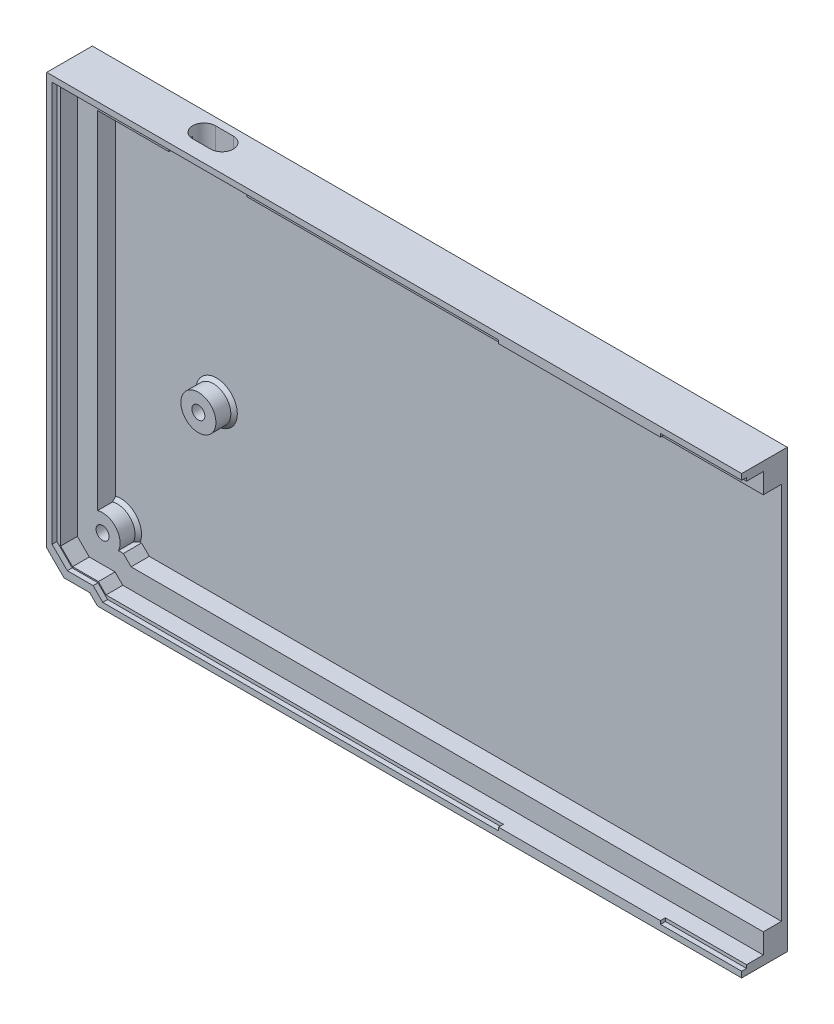
SolidWorks part; units mm, degrees
ref_plane "Přední rovina" through (0, 0, 0) normal (0, 0, 1) x (1, 0, 0)
ref_plane "Horní rovina" through (0, 0, 0) normal (0, 1, 0) x (1, 0, 0)
ref_plane "Pravá rovina" through (0, 0, 0) normal (1, 0, 0) x (0, 0, -1)
sketch "Skica3" plane through (0, 0, 0) normal (0, 0, 1) x (1, 0, 0)
  line L0 (0, 0) -> (415.1053, 0) construction
  line L1 (415.1053, 0) -> (416.6927, -1.5875) construction
  line L2 (416.6927, -1.5875) -> (416.6927, -119.8485) construction
  line L3 (0, 0) -> (-1.5875, -1.5875) construction
  line L4 (-1.5875, -1.5875) -> (-1.5875, -119.8485) construction
  line L5 (-1.5875, -119.8485) -> (0.7934, -122.2292) construction
  line L6 (0.7934, -122.2292) -> (8.7304, -122.2292) construction
  line L7 (8.7304, -122.2292) -> (11.1113, -124.61) construction
  line L8 (11.1113, -124.61) -> (403.9933, -124.61) construction
  line L9 (403.9933, -124.61) -> (406.3744, -122.2294) construction
  line L10 (406.3744, -122.2294) -> (414.3114, -122.2294) construction
  line L11 (416.6927, -119.8485) -> (414.3114, -122.2294) construction
  line L12 (2.4125, -4) -> (412.6927, -4)
  line L13 (412.6927, -4) -> (412.6927, -4)
  line L14 (412.6927, -4) -> (412.6927, -118.1914)
  line L15 (412.6927, -118.1914) -> (412.6547, -118.2294)
  line L16 (404.7177, -118.2294) -> (412.6547, -118.2294)
  line L17 (402.3367, -120.61) -> (404.7177, -118.2294)
  line L18 (12.7681, -120.61) -> (402.3367, -120.61)
  line L19 (10.3872, -118.2292) -> (12.7681, -120.61)
  line L20 (2.4502, -118.2292) -> (10.3872, -118.2292)
  line L21 (2.4125, -118.1915) -> (2.4502, -118.2292)
  line L22 (2.4125, -4) -> (2.4125, -118.1915)
  line L23 (2.4125, -4) -> (2.4125, -4)
  line L24 (-1.5875, -119.8485) -> (415.1053, 0) construction
  line L26 (0, 0) -> (416.6927, -119.8485) construction
  dimension "D1" = 135
  dimension "D2" = 135
  dimension "D3" = 4
  dimension "D4" = 2.245
  dimension "D5" = 2.245
  dimension "D6" = 118.261
  dimension "D7" = 118.261
  dimension "D8" = 3.367
  dimension "D9" = 7.937
  dimension "D10" = 3.367
  dimension "D11" = 392.882
  dimension "D12" = 3.367
  dimension "D13" = 7.937
  dimension "D14" = 3.3674
extrude "Přidat vysunutím1" add sketch "Skica3" along normal blind 5.6
shell "Skořepina1" thickness 1.8 removed face at (207.5525, -95.852, 5.6) outward yes
sketch "Skica7" plane through (0, 0, 5.6) normal (0, 0, 1) x (1, 0, 0)
  line L20 (-6.5875, 5) -> (-6.5875, -121.9196)
  line L21 (-6.5875, -121.9196) -> (-1.2775, -127.2292)
  line L22 (-1.2775, -127.2292) -> (6.6595, -127.2292)
  line L23 (6.6595, -127.2292) -> (9.0403, -129.61)
  line L24 (9.0403, -129.61) -> (406.0641, -129.61)
  line L25 (406.0641, -129.61) -> (408.4452, -127.2294)
  line L26 (408.4452, -127.2294) -> (416.3822, -127.2294)
  line L27 (416.3822, -127.2294) -> (421.6927, -121.9198)
  line L28 (421.6927, -121.9198) -> (421.6927, 5)
  line L29 (421.6927, 5) -> (-6.5875, 5)
  line L30 (-6.5875, 5) -> (-6.5875, -121.9196)
  line L31 (-6.5875, -121.9196) -> (-1.2775, -127.2292)
  line L32 (-1.2775, -127.2292) -> (6.6595, -127.2292)
  line L33 (6.6595, -127.2292) -> (9.0403, -129.61)
  line L34 (9.0403, -129.61) -> (406.0641, -129.61)
  line L35 (406.0641, -129.61) -> (408.4452, -127.2294)
  line L36 (408.4452, -127.2294) -> (416.3822, -127.2294)
  line L37 (416.3822, -127.2294) -> (421.6927, -121.9198)
  line L38 (421.6927, -121.9198) -> (421.6927, 5)
  line L39 (421.6927, 5) -> (-6.5875, 5)
  line L40 (-3.7875, 2.2) -> (-3.7875, -120.7598)
  line L41 (-3.7875, -120.7598) -> (-0.1178, -124.4292)
  line L42 (-0.1178, -124.4292) -> (7.8192, -124.4292)
  line L43 (7.8192, -124.4292) -> (10.2001, -126.81)
  line L44 (10.2001, -126.81) -> (404.9045, -126.81)
  line L45 (404.9045, -126.81) -> (407.2855, -124.4294)
  line L46 (407.2855, -124.4294) -> (415.2225, -124.4294)
  line L47 (415.2225, -124.4294) -> (418.8927, -120.7598)
  line L48 (418.8927, -120.7598) -> (418.8927, 2.2)
  line L49 (418.8927, 2.2) -> (-3.7875, 2.2)
  line L50 (-3.7875, 2.2) -> (-3.7875, -120.7598)
  line L51 (-3.7875, -120.7598) -> (-0.1178, -124.4292)
  line L52 (-0.1178, -124.4292) -> (7.8192, -124.4292)
  line L53 (7.8192, -124.4292) -> (10.2001, -126.81)
  line L54 (10.2001, -126.81) -> (404.9045, -126.81)
  line L55 (404.9045, -126.81) -> (407.2855, -124.4294)
  line L56 (407.2855, -124.4294) -> (415.2225, -124.4294)
  line L57 (415.2225, -124.4294) -> (418.8927, -120.7598)
  line L58 (418.8927, -120.7598) -> (418.8927, 2.2)
  line L59 (418.8927, 2.2) -> (-3.7875, 2.2)
  dimension "D2" = 4.4
  dimension "D1" = 7.2
extrude "Přidat vysunutím3" add sketch "Skica7" along normal blind 5.15 separate body
sketch "Skica8" plane through (0, 0, 5.6) normal (0, 0, -1) x (-1, 0, 0)
  line L0 (-421.6927, 5) -> (6.5875, 5)
  line L1 (6.5875, 5) -> (6.5875, -121.9196)
  line L2 (6.5875, 5) -> (6.5875, -121.9196) construction
  line L3 (6.5875, -121.9196) -> (1.2775, -127.2292)
  line L4 (1.2775, -127.2292) -> (-6.6595, -127.2292)
  line L5 (-6.6595, -127.2292) -> (-9.0403, -129.61)
  line L6 (-9.0403, -129.61) -> (-406.0641, -129.61)
  line L7 (-406.0641, -129.61) -> (-408.4452, -127.2294)
  line L8 (-408.4452, -127.2294) -> (-416.3822, -127.2294)
  line L9 (-416.3822, -127.2294) -> (-421.6927, -121.9198)
  line L10 (-421.6927, -121.9198) -> (-421.6927, 5)
  line L11 (-0.6125, -2.2) -> (-0.6125, -118.9371)
  line L12 (-414.4927, -2.2) -> (-0.6125, -2.2) construction
  line L13 (-0.6125, -2.2) -> (-0.6125, -118.9371) construction
  line L14 (-0.6125, -118.9371) -> (-1.7047, -120.0292)
  line L15 (-1.7047, -120.0292) -> (-9.6417, -120.0292)
  line L16 (-9.6417, -120.0292) -> (-12.0226, -122.41)
  line L17 (-12.0226, -122.41) -> (-403.0822, -122.41)
  line L18 (-403.0822, -122.41) -> (-405.4632, -120.0294)
  line L19 (-405.4632, -120.0294) -> (-413.4002, -120.0294) construction
  line L20 (-405.4632, -120.0294) -> (-413.4002, -120.0294)
  line L21 (-413.4002, -120.0294) -> (-414.4927, -118.9371) construction
  line L22 (-413.4002, -120.0294) -> (-414.4927, -118.9371)
  line L23 (-414.4927, -118.9371) -> (-414.4927, -2.2)
  line L24 (-414.4927, -2.2) -> (-0.6125, -2.2)
extrude "Přidat vysunutím4" add sketch "Skica8" along normal up to surface (7.4 mm away) up to face at (207.5525, -96.7211, -1.8)
sketch "Skica11" plane through (0, 0, 10.75) normal (0, 0, 1) x (1, 0, 0)
  line L0 (207.5526, 3.195) -> (207.5526, 5) construction
  line L1 (421.6927, 5) -> (-6.5875, 5) construction
  line L2 (207.5522, -127.805) -> (207.5522, -129.61) construction
  line L3 (9.0403, -129.61) -> (406.0641, -129.61) construction
  line L4 (-4.9474, -58.4598) -> (-6.5875, -58.4598) construction
  line L5 (-6.5875, 5) -> (-6.5875, -121.9196) construction
  line L6 (420.0526, -58.4599) -> (421.6927, -58.4599) construction
  line L7 (421.6927, -121.9198) -> (421.6927, 5) construction
  line L8 (404.9045, -126.81) -> (407.2855, -124.4294) construction
  line L9 (415.2225, -124.4294) -> (418.8927, -120.7598) construction
  line L10 (7.8192, -124.4292) -> (10.2001, -126.81) construction
  line L11 (-3.7875, -120.7598) -> (-0.1178, -124.4292) construction
  line L13 (407.2855, -124.4294) -> (415.2225, -124.4294) construction
  line L14 (-0.1178, -124.4292) -> (7.8192, -124.4292) construction
  line L30 (420.0526, 3.195) -> (-4.9474, 3.195)
  line L31 (-4.9474, 3.195) -> (-4.9474, -120.1146)
  line L32 (-4.9474, -120.1146) -> (-0.24, -124.8217)
  line L33 (-0.24, -124.8217) -> (7.697, -124.8217)
  line L34 (7.697, -124.8217) -> (10.6804, -127.805)
  line L35 (10.6804, -127.805) -> (404.4241, -127.805)
  line L36 (404.4241, -127.805) -> (406.8051, -125.4244)
  line L37 (406.8051, -125.4244) -> (414.7421, -125.4244)
  line L38 (414.7421, -125.4244) -> (420.0526, -120.1148)
  line L39 (420.0526, -120.1148) -> (420.0526, 3.195)
  line L45 (421.6927, 5) -> (-6.5875, 5)
  line L46 (-6.5875, 5) -> (-6.5875, -121.9196)
  line L47 (-6.5875, -121.9196) -> (-1.2775, -127.2292)
  line L48 (-1.2775, -127.2292) -> (6.6595, -127.2292)
  line L49 (6.6595, -127.2292) -> (9.0403, -129.61)
  line L50 (9.0403, -129.61) -> (406.0641, -129.61)
  line L51 (406.0641, -129.61) -> (408.4452, -127.2294)
  line L52 (408.4452, -127.2294) -> (416.3822, -127.2294)
  line L53 (416.3822, -127.2294) -> (421.6927, -121.9198)
  line L54 (421.6927, -121.9198) -> (421.6927, 5)
  line L55 (421.6927, 5) -> (-6.5875, 5)
  line L56 (-6.5875, 5) -> (-6.5875, -121.9196)
  line L57 (-6.5875, -121.9196) -> (-1.2775, -127.2292)
  line L58 (-1.2775, -127.2292) -> (6.6595, -127.2292)
  line L59 (6.6595, -127.2292) -> (9.0403, -129.61)
  line L60 (9.0403, -129.61) -> (406.0641, -129.61)
  line L61 (406.0641, -129.61) -> (408.4452, -127.2294)
  line L62 (408.4452, -127.2294) -> (416.3822, -127.2294)
  line L63 (416.3822, -127.2294) -> (421.6927, -121.9198)
  line L64 (421.6927, -121.9198) -> (421.6927, 5)
  point P0 (207.5523, -63.11)
  point P2 (207.5523, -63.11)
  dimension "D1" = 131
  dimension "D2" = 425
  dimension "D3" = 0
extrude "Přidat vysunutím5" add sketch "Skica11" along normal blind 1.5
sketch "Skica14" plane through (0, 0, 10.75) normal (0, 0, 1) x (1, 0, 0)
  line L0 (418.8927, 2.2) -> (-3.7875, 2.2) construction
  line L1 (182.5326, 2.2) -> (132.6326, 2.2)
  line L2 (182.5326, 2.2) -> (182.5326, 3.195)
  line L3 (182.5326, 3.195) -> (132.6326, 3.195)
  line L4 (132.6326, 2.2) -> (132.6326, 3.195)
  line L5 (420.0526, 3.195) -> (-4.9474, 3.195) construction
  line L6 (418.8927, 2.2) -> (-3.7875, 2.2) construction
  line L7 (232.5726, 2.2) -> (282.4726, 2.2)
  line L8 (232.5726, 2.2) -> (232.5726, 3.195)
  line L9 (232.5726, 3.195) -> (282.4726, 3.195)
  line L10 (282.4726, 2.2) -> (282.4726, 3.195)
  line L11 (207.5526, 3.195) -> (207.5522, -127.805) construction
  line L12 (10.6804, -127.805) -> (404.4241, -127.805) construction
  line L13 (10.2001, -126.81) -> (404.9045, -126.81) construction
  line L14 (232.5722, -126.81) -> (282.4722, -126.81)
  line L15 (232.5722, -126.81) -> (232.5722, -127.805)
  line L16 (232.5722, -127.805) -> (282.4722, -127.805)
  line L17 (282.4722, -126.81) -> (282.4722, -127.805)
  line L18 (10.6804, -127.805) -> (404.4241, -127.805) construction
  line L20 (182.5322, -126.81) -> (132.6322, -126.81)
  line L21 (182.5322, -126.81) -> (182.5322, -127.805)
  line L22 (182.5322, -127.805) -> (132.6322, -127.805)
  line L23 (132.6322, -126.81) -> (132.6322, -127.805)
  dimension "D1" = 49.9
  dimension "D2" = 49.9
  dimension "D3" = 25.02
  dimension "D4" = 25.02
  dimension "D5" = 49.9
  dimension "D6" = 49.9
  dimension "D7" = 25.02
  dimension "D8" = 25.02
extrude "Přidat vysunutím6" add sketch "Skica14" along normal up to surface (1.5 mm away) up to face at (207.5524, -100.1977, 12.25)
sketch "Skica15" plane through (0, 0, 0) normal (0, 0, 1) x (1, 0, 0)
  line L1 (34.9015, 4.5) -> (37.9015, 4.5)
  line L2 (34.9015, 4.5) -> (34.9015, -4.5)
  line L3 (34.9015, -4.5) -> (37.9015, -4.5)
  line L4 (37.9015, 4.5) -> (37.9015, -4.5)
  line L5 (34.9015, 4.5) -> (37.9015, -4.5) construction
  line L6 (34.9015, -4.5) -> (37.9015, 4.5) construction
  line L20 (-1.5875, 0) -> (-1.5875, -119.8485)
  line L21 (-1.5875, -119.8485) -> (0.7934, -122.2292)
  line L22 (0.7934, -122.2292) -> (8.7304, -122.2292)
  line L23 (8.7304, -122.2292) -> (11.1113, -124.61)
  line L24 (11.1113, -124.61) -> (403.9933, -124.61)
  line L25 (403.9933, -124.61) -> (406.3744, -122.2294)
  line L26 (406.3744, -122.2294) -> (414.3114, -122.2294)
  line L27 (414.3114, -122.2294) -> (416.6927, -119.8485)
  line L28 (416.6927, -119.8485) -> (416.6927, 0)
  line L29 (416.6927, 0) -> (-1.5875, 0)
  line L30 (-1.5875, 0) -> (-1.5875, -119.8485) construction
  line L31 (-1.5875, -119.8485) -> (0.7934, -122.2292) construction
  line L32 (0.7934, -122.2292) -> (8.7304, -122.2292) construction
  line L33 (8.7304, -122.2292) -> (11.1113, -124.61) construction
  line L34 (11.1113, -124.61) -> (403.9933, -124.61) construction
  line L35 (403.9933, -124.61) -> (406.3744, -122.2294) construction
  line L36 (406.3744, -122.2294) -> (414.3114, -122.2294) construction
  line L37 (414.3114, -122.2294) -> (416.6927, -119.8485) construction
  line L38 (416.6927, -119.8485) -> (416.6927, 0) construction
  line L39 (416.6927, 0) -> (-1.5875, 0) construction
  circle A0 centre (3.9685, -115.9542) radius 5.4
  circle A1 centre (33.4915, -69.051) radius 5.4
  circle A2 centre (411.1977, -115.8794) radius 5.4
  circle A3 centre (334.1477, -53.972) radius 5.4
  point P2 (-1.4315, -115.9542)
  point P3 (3.9685, -121.3542)
  point P4 (28.0915, -69.051)
  point P8 (33.4915, -74.451)
  point P12 (411.1977, -121.2794)
  point P13 (416.5977, -115.8794)
  point P17 (334.1477, -48.572)
  point P19 (339.5477, -53.972)
  point P21 (36.4015, 0)
  point P23 (36.4015, 0)
  dimension "D2" = 0.156
  dimension "D4" = 10.8
  dimension "D7" = 10.8
  dimension "D10" = 10.8
  dimension "D13" = 10.8
  dimension "D3" = 0.875
  dimension "D5" = 29.679
  dimension "D6" = 50.159
  dimension "D8" = 0.095
  dimension "D9" = 0.95
  dimension "D11" = 77.145
  dimension "D12" = 48.572
  dimension "D14" = 37.989
  dimension "D15" = 9
  dimension "D16" = 3
  dimension "D1" = 4
extrude "Přidat vysunutím7" add sketch "Skica15" along normal blind 5.6
sketch "Skica16" plane through (0, 0, 5.6) normal (0, 0, 1) x (1, 0, 0)
  circle A0 centre (3.9685, -115.9542) radius 2
  circle A1 centre (33.4915, -69.051) radius 2
  circle A2 centre (334.1477, -53.972) radius 2
  circle A3 centre (411.1977, -115.8794) radius 2
  dimension "D1" = 4
  dimension "D2" = 4
  dimension "D3" = 4
  dimension "D4" = 4
extrude "Odebrat vysunutím1" cut sketch "Skica16" against normal blind 5.75
chamfer "Zkosení1" distance 1 angle 45 4 edges at (407.0694, -112.3984, 0) (8.0492, -112.4175, 0) (38.8915, -69.051, 0) (339.5477, -53.972, 0)
sketch "Skica17" plane through (0, 0, 5.6) normal (0, 0, 1) x (1, 0, 0)
  line L0 (34.9015, -4.5) -> (37.9015, -4.5) construction
  line L1 (24.4015, -11.2) -> (48.4015, -11.2)
  line L2 (24.4015, -11.2) -> (24.4015, 2.2)
  line L3 (24.4015, 2.2) -> (48.4015, 2.2)
  line L4 (48.4015, -11.2) -> (48.4015, 2.2)
  line L5 (24.4015, -11.2) -> (48.4015, 2.2) construction
  line L6 (24.4015, 2.2) -> (48.4015, -11.2) construction
  line L7 (418.8927, 2.2) -> (-3.7875, 2.2) construction
  point P0 (36.4015, -4.5)
  dimension "D1" = 24
extrude "Odebrat vysunutím2" cut sketch "Skica17" against normal blind 1.6
sketch "Skica18" plane through (0, -4.5, 0) normal (0, -1, 0) x (1, 0, 0)
  line L0 (33.6515, 4) -> (39.1515, 4) construction
  line L1 (37.9015, 4) -> (34.9015, 4) construction
  line L2 (37.9015, 4) -> (48.4015, 4) construction
  line L3 (33.6515, 7.5) -> (39.1515, 7.5)
  line L4 (33.6515, 0.5) -> (39.1515, 0.5)
  arc A0 (33.6515, 7.5) -> (33.6515, 0.5) centre (33.6515, 4) ccw
  arc A1 (39.1515, 0.5) -> (39.1515, 7.5) centre (39.1515, 4) ccw
  point P6 (36.4015, 4)
  point P11 (30.1515, 4)
  point P12 (42.6515, 4)
  dimension "D1" = 12.5
  dimension "D2" = 7
extrude "Odebrat vysunutím3" cut sketch "Skica18" against normal up to surface (9.5 mm away) up to face at (207.5526, 5, 5.225)
sketch "Skica23" plane through (-6.5875, 0, 0) normal (-1, 0, 0) x (0, 0, 1)
  line L2 (-1.8, 5) -> (-1.8, -121.9196) construction
  line L4 (-1.8, -58.4598) -> (12.25, -58.4598) construction
  line L5 (12.25, 5) -> (12.25, -121.9196) construction
  circle A0 centre (3.2, -18.4598) radius 2
  circle A1 centre (3.2, -98.4598) radius 2
  point P8 (-1.8, -58.4598)
  dimension "D2" = 4
  dimension "D3" = 4
  dimension "D1" = 40
  dimension "D4" = 5
extrude "Odebrat vysunutím4" cut sketch "Skica23" against normal blind 5.7
sketch "Skica24" plane through (421.6927, 0, 0) normal (1, 0, 0) x (0, 0, -1)
  line L0 (1.8, -58.4599) -> (-12.25, -58.4599) construction
  line L1 (1.8, -121.9198) -> (1.8, 5) construction
  line L2 (-12.25, -121.9198) -> (-12.25, 5) construction
  circle A0 centre (-3.2, -18.4599) radius 2
  circle A1 centre (-3.2, -98.4599) radius 2
  dimension "D1" = 4
  dimension "D2" = 4
  dimension "D3" = 40
  dimension "D4" = 5
extrude "Odebrat vysunutím5" cut sketch "Skica24" against normal blind 5.7
sketch "Skica25" plane through (0, 0, -1.8) normal (0, 0, -1) x (-1, 0, 0)
  line L0 (-421.6927, -121.9198) -> (-421.6927, 5) construction
  line L1 (-421.6927, 5) -> (6.5875, 5) construction
  line L2 (6.5875, 5) -> (6.5875, -121.9196) construction
  line L3 (-9.0403, -129.61) -> (-406.0641, -129.61) construction
  circle A0 centre (-401.6927, -15) radius 6.25
  circle A1 centre (-13.4125, -15) radius 6.25
  circle A2 centre (-388.4452, -109.61) radius 6.25
  circle A3 centre (-26.6595, -109.61) radius 6.25
  dimension "D1" = 12.5
  dimension "D2" = 12.5
  dimension "D3" = 12.5
  dimension "D4" = 12.5
  dimension "D5" = 20
  dimension "D6" = 20
  dimension "D7" = 20
  dimension "D8" = 20
  dimension "D9" = 20
  dimension "D10" = 20
  dimension "D11" = 20
  dimension "D12" = 20
extrude "Odebrat vysunutím6" cut sketch "Skica25" against normal blind 1.5
sketch "Skica26" plane through (0, 5, 0) normal (0, 1, 0) x (1, 0, 0)
  line L0 (207.5526, 1.8) -> (207.5526, -12.25)
  line L1 (421.6927, 1.8) -> (-6.5875, 1.8) construction
  line L2 (421.6927, -12.25) -> (-6.5875, -12.25) construction
  line L3 (207.5526, -12.25) -> (421.6927, -12.25)
  line L4 (421.6927, -12.25) -> (421.6927, 1.8)
  line L5 (421.6927, 1.8) -> (207.5526, 1.8)
extrude "Odebrat vysunutím7" cut sketch "Skica26" against normal through all
